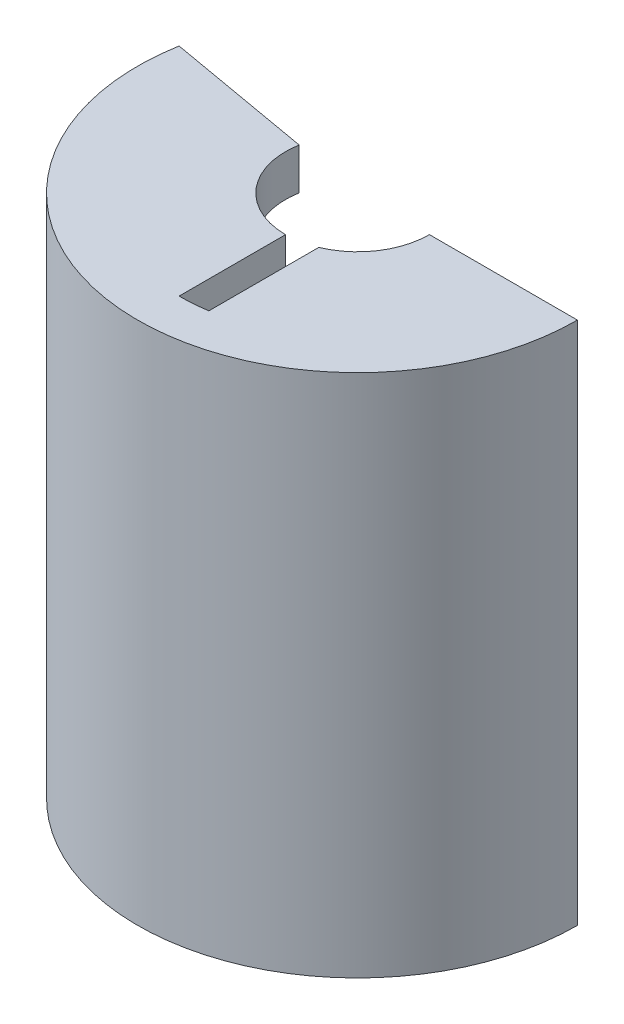
SolidWorks part; units mm, degrees
ref_plane "Front Plane" through (0, 0, 0) normal (0, 0, 1) x (1, 0, 0)
ref_plane "Top Plane" through (0, 0, 0) normal (0, 1, 0) x (1, 0, 0)
ref_plane "Right Plane" through (0, 0, 0) normal (1, 0, 0) x (0, 0, -1)
sketch "Sketch1" plane through (0, 0, 0) normal (0, 0, 1) x (1, 0, 0)
  line L0 (5.2, 99.643) -> (12.8971, 99.643)
  line L1 (12.8971, 99.643) -> (12.8971, 77.4)
  line L2 (12.8971, 77.4) -> (9.725, 77.4)
  line L3 (9.725, 77.4) -> (9.725, 67.748)
  line L4 (9.725, 67.748) -> (2.7, 67.748)
  line L5 (2.7, 67.748) -> (2.7, 64.748)
  line L6 (2.7, 64.748) -> (15.8971, 64.748)
  line L7 (15.8971, 64.748) -> (15.8971, 102.643)
  line L8 (15.8971, 102.643) -> (5.2, 102.643)
  line L9 (5.2, 102.643) -> (5.2, 99.643)
  line L10 (12.1887, 99.543) -> (-12.1584, 99.543) construction
  line L11 (-9.1223, 67.848) -> (9.1425, 67.848) construction
  line L12 (6.6833, 77.5) -> (11.6955, 77.5) construction
  line L13 (9.525, 68.229) -> (9.525, 77.119) construction
  line L14 (12.6971, 91.5674) -> (12.6971, 99.035) construction
  line L15 (5, 215.6886) -> (5, 216.8136) construction
  line L17 (2.5, 55) -> (2.5, 77.2) construction
  dimension "D1" = 0.1
  dimension "D2" = 0.1
  dimension "D3" = 0.1
  dimension "D4" = 0.2
  dimension "D5" = 0.2
  dimension "D6" = 3
  dimension "D7" = 3
  dimension "D8" = 3
  dimension "D9" = 0.2
  dimension "D10" = 0.2
ref_axis "Axis1" through (0, 104.5377, 0) along (0, -1, 0)
revolve "Revolve1" add sketch "Sketch1" angle 190 about axis through (0, 104.5377, 0) along (0, -1, 0) region at (5.6013, 101.143, 0)
sketch "Sketch2" plane through (0, 102.643, 0) normal (0, 1, 0) x (1, 0, 0)
  line L0 (0, 0) -> (0, -12.8971)
  line L1 (0, 0) -> (1.9992, 0)
  line L2 (1.9992, 0) -> (1.9992, -12.7412)
  arc A0 (-12.7012, 2.2396) -> (12.8971, 0) centre (0, 0) ccw construction
  arc A1 (0, -12.8971) -> (1.9992, -12.7412) centre (0, 0) ccw
extrude "Cut-Extrude1" cut sketch "Sketch2" against normal through all
